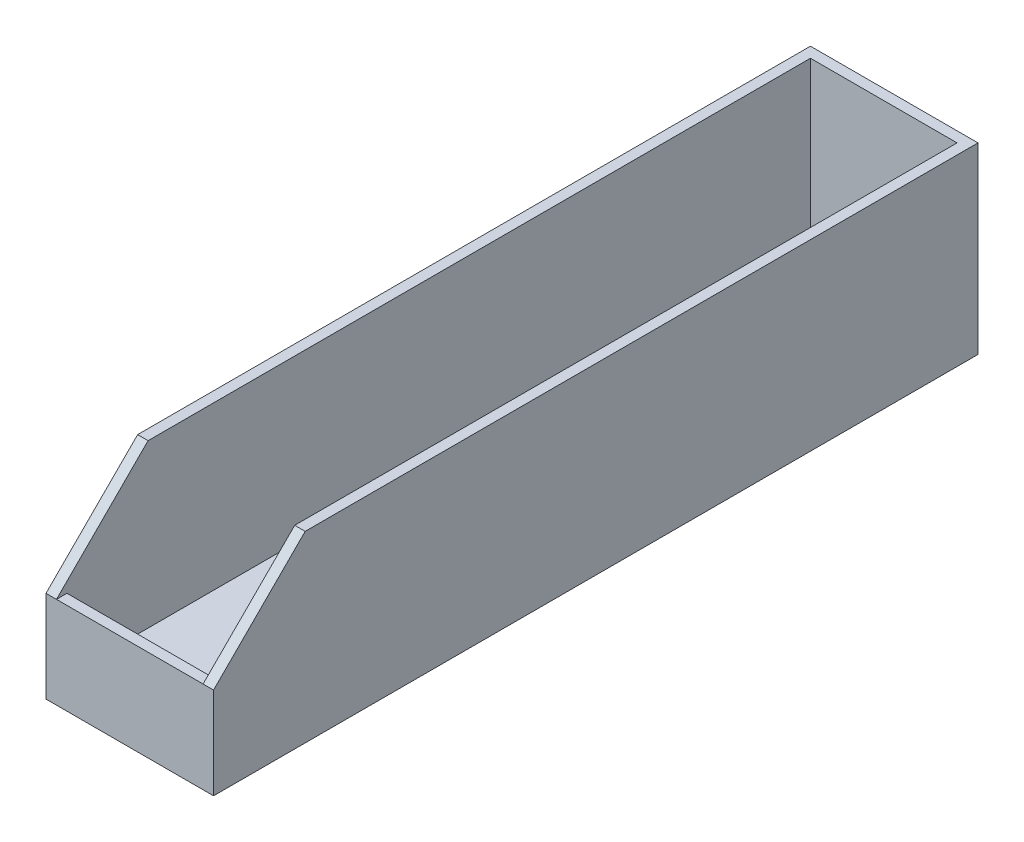
SolidWorks part; units mm, degrees
ref_plane "Front Plane" through (0, 0, 0) normal (0, 0, 1) x (1, 0, 0)
ref_plane "Top Plane" through (0, 0, 0) normal (0, 1, 0) x (1, 0, 0)
ref_plane "Right Plane" through (0, 0, 0) normal (1, 0, 0) x (0, 0, -1)
sketch "Sketch1" plane through (0, 0, 0) normal (0, 1, 0) x (1, 0, 0)
  line L0 (-14, -71) -> (-14, -73)
  line L1 (-16, 73) -> (16, 73)
  line L2 (-16, 73) -> (-16, -73)
  line L3 (-16, -73) -> (16, -73)
  line L4 (16, 73) -> (16, -73)
  line L5 (-16, 73) -> (16, -73) construction
  line L6 (-16, -73) -> (16, 73) construction
  line L7 (-14, 71) -> (14, 71)
  line L8 (-14, 71) -> (-14, -71)
  line L9 (-14, -71) -> (14, -71)
  line L10 (14, 71) -> (14, -71)
  line L11 (-14, 71) -> (14, -71) construction
  line L12 (-14, -71) -> (14, 71) construction
  line L13 (14, -71) -> (14, -73)
  point P0 (0, 0)
  point P6 (0, 0)
  dimension "D1" = 146
  dimension "D2" = 28
  dimension "D3" = 32
  dimension "D4" = 142
extrude "Boss-Extrude1" add sketch "Sketch1" along normal blind 4 contours L10 L7 L8 L9 region at (0, 0, 0)
extrude "Boss-Extrude2" add sketch "Sketch1<4>" along normal blind 35 contours L10 L13 L3 L4 L1 L2 L0 L8 L7 region at (-15.4947, 0, 72)
sketch "Sketch1<4>" plane through (0, 0, 0) normal (0, 1, 0) x (1, 0, 0) same geometry as "Sketch1"
extrude "Boss-Extrude3" add sketch "Sketch1<5>" along normal blind 17.5 contours L13 L9 L0 L3 region at (0, 0, 72)
sketch "Sketch1<5>" plane through (0, 0, 0) normal (0, 1, 0) x (1, 0, 0) same geometry as "Sketch1"
sketch "Sketch2" plane through (0, 4, 0) normal (0, 1, 0) x (1, 0, 0)
  line L0 (0, 30) -> (0, -30) construction
  circle A0 centre (0, 30) radius 3.05
  circle A1 centre (0, 30) radius 1.7
  circle A2 centre (0, -30) radius 3.05
  circle A3 centre (0, -30) radius 1.7
  point P6 (0, 0)
  dimension "D1" = 3.4
  dimension "D2" = 6.1
  dimension "D3" = 30
extrude "Cut-Extrude1" cut sketch "Sketch2" against normal up to next contours A1 | A3 region at (0, 4, -30) region at (0, 4, 30)
extrude "Cut-Extrude2" cut sketch "Sketch2<3>" against normal blind 2 contours A2 A3 | A1 A0 region at (-2.9637, 4, -30) region at (-2.9637, 4, 30)
sketch "Sketch2<3>" plane through (0, 4, 0) normal (0, 1, 0) x (1, 0, 0) same geometry as "Sketch2"
sketch "Sketch3" plane through (16, 0, 0) normal (1, 0, 0) x (0, 0, -1)
  line L0 (-73, 17.5) -> (-55.5, 35)
  line L1 (-73, 35) -> (-73, 0) construction
  line L2 (73, 35) -> (-73, 35) construction
  line L3 (-55.5, 35) -> (-73, 35)
  line L4 (-73, 35) -> (-73, 17.5)
extrude "Cut-Extrude3" cut sketch "Sketch3" against normal through all
